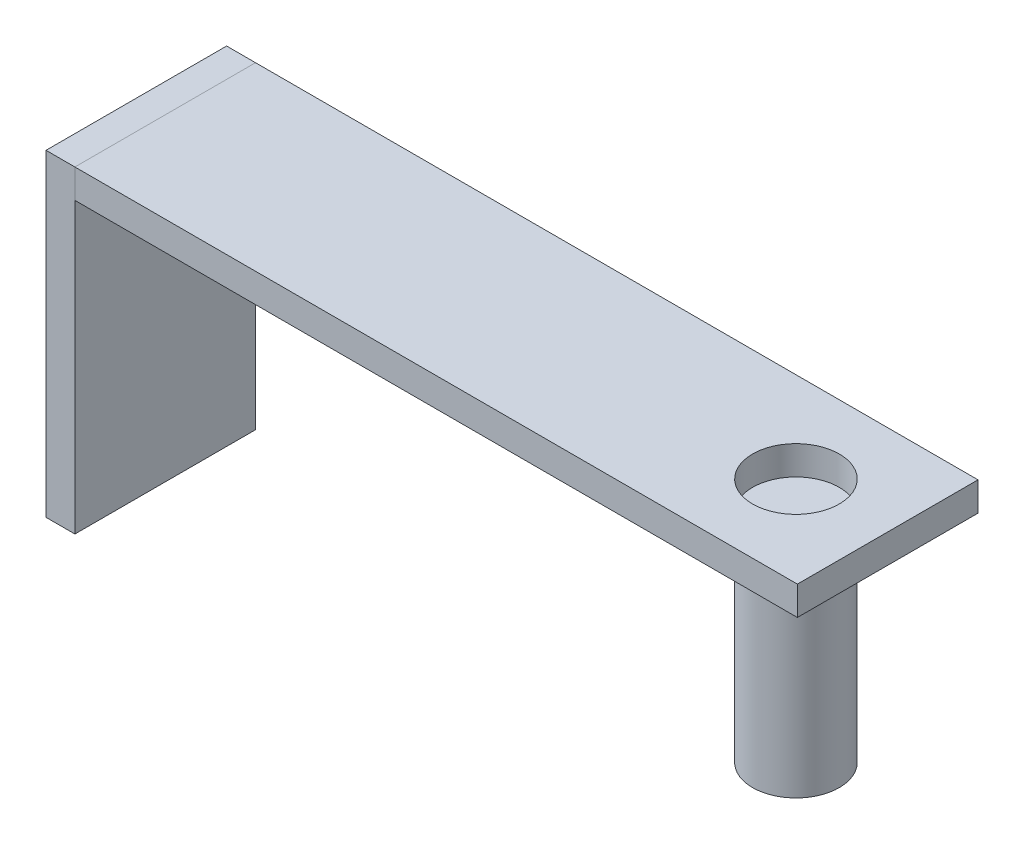
SolidWorks part; units mm, degrees
ref_plane "Front Plane" through (0, 0, 0) normal (0, 0, 1) x (1, 0, 0)
ref_plane "Top Plane" through (0, 0, 0) normal (0, 1, 0) x (1, 0, 0)
ref_plane "Right Plane" through (0, 0, 0) normal (1, 0, 0) x (0, 0, -1)
sketch "Sketch1" plane through (0, 0, 0) normal (0, 1, 0) x (1, 0, 0)
  line L0 (-25, 0) -> (18.65, 0) construction
  line L1 (-25, 6.25) -> (25, 6.25)
  line L2 (-25, 6.25) -> (-25, -6.25)
  line L3 (-25, -6.25) -> (25, -6.25)
  line L4 (25, 6.25) -> (25, -6.25)
  line L5 (-25, 6.25) -> (25, -6.25) construction
  line L6 (-25, -6.25) -> (25, 6.25) construction
  line L8 (-25, -6.25) -> (-27, -6.25)
  line L9 (-25, -6.25) -> (-25, 6.25)
  line L10 (-25, 6.25) -> (-27, 6.25)
  line L11 (-27, -6.25) -> (-27, 6.25)
  circle A0 centre (18.65, 0) radius 3
  point P0 (0, 0)
  dimension "D4" = 6
  dimension "D1" = 50
  dimension "D2" = 12.5
  dimension "D3" = 43.65
  dimension "D5" = 2
extrude "Boss-Extrude6" add sketch "Sketch1" against normal blind 20 and the other way blind 2 contours L11 L8 L2 L10 region at (-26, 0, 0)
extrude "Boss-Extrude7" add sketch "Sketch1<4>" along normal blind 2 separate body contours L4 L1 L2 L3 A0 region at (-0.8837, 0, 0)
sketch "Sketch1<4>" plane through (0, 0, 0) normal (0, 1, 0) x (1, 0, 0) same geometry as "Sketch1"
extrude "Boss-Extrude8" add sketch "Sketch1<5>" against normal blind 15 separate body contours A0 region at (18.65, 0, 0)
sketch "Sketch1<5>" plane through (0, 0, 0) normal (0, 1, 0) x (1, 0, 0) same geometry as "Sketch1"
